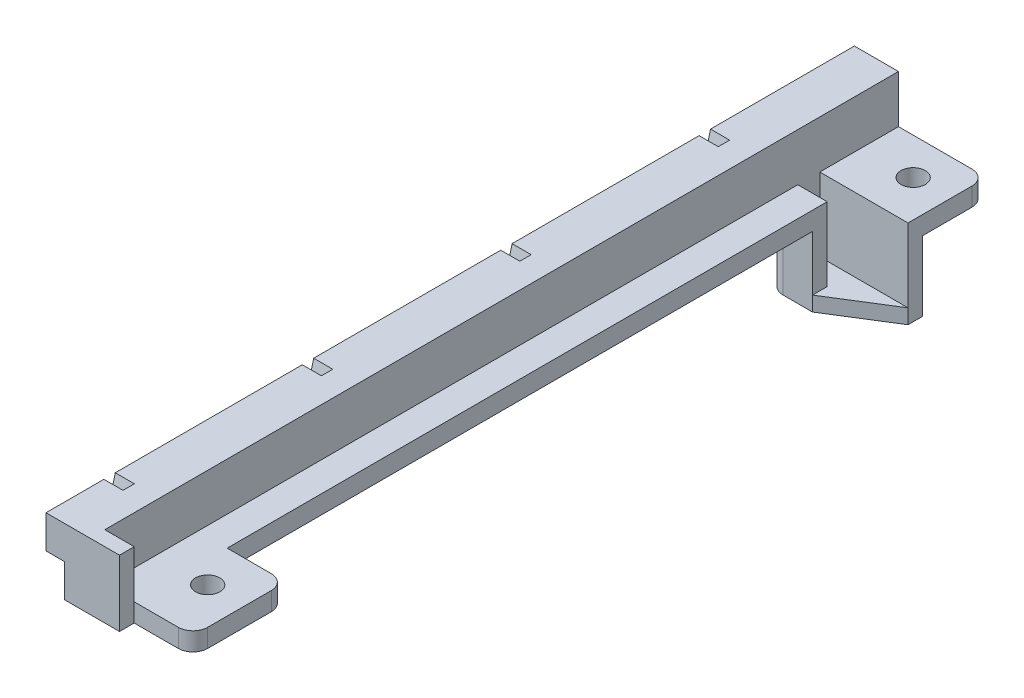
SolidWorks part; units mm, degrees
ref_plane "Front Plane" through (0, 0, 0) normal (0, 0, 1) x (1, 0, 0)
ref_plane "Top Plane" through (0, 0, 0) normal (0, 1, 0) x (1, 0, 0)
ref_plane "Right Plane" through (0, 0, 0) normal (1, 0, 0) x (0, 0, -1)
sketch "Side lip main section" plane through (0, 0, 0) normal (0, 1, 0) x (1, 0, 0)
  line L1 (0, 0) -> (6, 0)
  line L2 (0, 0) -> (0, -108)
  line L3 (0, -108) -> (6, -108)
  line L4 (6, 0) -> (6, -108)
  dimension "D1" = 6
  dimension "D2" = 108
extrude "Side lip" add sketch "Side lip main section" against normal blind 5
sketch "Sketch2" plane through (0, 0, 0) normal (-1, 0, 0) x (0, 0, 1)
  line L0 (102, 0) -> (103.2466, -5)
  line L1 (0, 0) -> (108, 0) construction
  line L2 (0, -5) -> (108, -5) construction
  line L3 (100.4541, 0) -> (101.7007, -5)
  line L4 (75, 0) -> (76.2466, -5)
  line L5 (73.4541, 0) -> (74.7007, -5)
  line L6 (48, 0) -> (49.2466, -5)
  line L7 (46.4541, 0) -> (47.7007, -5)
  line L8 (21, 0) -> (22.2466, -5)
  line L9 (19.4541, 0) -> (20.7007, -5)
  line L10 (21, 0) -> (19.5446, -0.3629) construction
  line L11 (48, 0) -> (46.5446, -0.3629) construction
  line L12 (75, 0) -> (73.5446, -0.3629) construction
  line L13 (102, 0) -> (100.5446, -0.3629) construction
  line L14 (102, 0) -> (102, -5) construction
  line L15 (108, -5) -> (108, 0) construction
  line L16 (75, 0) -> (75, -5) construction
  line L17 (48, 0) -> (48, -5) construction
  line L18 (21, 0) -> (21, -5) construction
  line L19 (19.4541, 0) -> (21, 0)
  line L20 (20.7007, -5) -> (22.2466, -5)
  line L21 (47.7007, -5) -> (49.2466, -5)
  line L22 (46.4541, 0) -> (48, 0)
  line L23 (73.4541, 0) -> (75, 0)
  line L24 (74.7007, -5) -> (76.2466, -5)
  line L25 (100.4541, 0) -> (102, 0)
  line L26 (101.7007, -5) -> (103.2466, -5)
  dimension "D1" = 1.5
  dimension "D2" = 76
  dimension "D3" = 6
  dimension "D4" = 27
  dimension "D5" = 54
  dimension "D6" = 81
extrude "Vertical fin cuts" cut sketch "Sketch2" against normal blind 2.6
sketch "Sketch4" plane through (0, -5, 0) normal (0, -1, 0) x (1, 0, 0)
  line L0 (6, 0) -> (0, 0) construction
  line L1 (6, 108) -> (2.5, 108)
  line L2 (6, 108) -> (6, 0)
  line L3 (6, 0) -> (2.5, 0)
  line L4 (2.5, 108) -> (2.5, 0)
  dimension "D1" = 3.5
extrude "Descender" add sketch "Sketch4" along normal blind 4.5
sketch "Sketch5" plane through (6, 0, 0) normal (1, 0, 0) x (0, 0, -1)
  line L0 (0, -9.5) -> (0, 0) construction
  line L1 (-108, -9.5) -> (0, -9.5)
  line L2 (-108, -9.5) -> (-108, -7)
  line L3 (-108, -7) -> (0, -7)
  line L4 (0, -9.5) -> (0, -7)
  dimension "D1" = 2.5
extrude "PCB base" add sketch "Sketch5" along normal blind 4
sketch "Sketch8" plane through (0, 0, 108) normal (0, 0, 1) x (1, 0, 0)
  line L1 (6, 0) -> (10, 0)
  line L4 (10, 0) -> (10, -7)
  line L8 (6, 0) -> (0, 0)
  line L9 (0, 0) -> (0, -5)
  line L10 (0, -5) -> (2.5, -5)
  line L11 (2.5, -5) -> (2.5, -9.5)
  line L12 (2.5, -9.5) -> (10, -9.5)
  line L13 (10, -9.5) -> (10, -7)
  line L14 (10, -7) -> (6, -7)
  line L15 (6, -7) -> (6, 0)
  line L16 (6, 0) -> (0, 0)
  line L17 (0, 0) -> (0, -5)
  line L18 (0, -5) -> (2.5, -5)
  line L19 (2.5, -5) -> (2.5, -9.5)
  line L20 (2.5, -9.5) -> (10, -9.5)
  line L21 (10, -9.5) -> (10, -7)
  dimension "D1" = 0
extrude "Lower cap" add sketch "Sketch8" along normal blind 2
sketch "Sketch9" plane through (10, 0, 0) normal (1, 0, 0) x (0, 0, -1)
  line L0 (0, -7) -> (-108, -7) construction
  line L1 (-13.7, -7) -> (-10.7, -7)
  line L2 (-13.7, -7) -> (-13.7, -9.5)
  line L3 (-13.7, -9.5) -> (-10.7, -9.5)
  line L4 (-10.7, -7) -> (-10.7, -9.5)
  line L5 (-110, -9.5) -> (0, -9.5) construction
  line L6 (-108, -7) -> (-108, 0) construction
  dimension "D1" = 94.3
  dimension "D2" = 3
extrude "Al bar cut" cut sketch "Sketch9" against normal blind 4
sketch "Sketch10" plane through (10, 0, 0) normal (1, 0, 0) x (0, 0, -1)
  line L0 (-110, -9.5) -> (-13.7, -9.5) construction
  line L1 (-108, -7) -> (-95.3463, -7)
  line L2 (-108, -7) -> (-108, -9.5)
  line L3 (-108, -9.5) -> (-95.3463, -9.5)
  line L4 (-95.3463, -7) -> (-95.3463, -9.5)
  line L6 (-10.7, -7) -> (0, -7)
  line L7 (-10.7, -7) -> (-10.7, -9.5)
  line L8 (-10.7, -9.5) -> (0, -9.5)
  line L9 (0, -7) -> (0, -9.5)
extrude "Support tabs" add sketch "Sketch10" along normal blind 8
sketch "Sketch11" plane through (0, -7, 0) normal (0, 1, 0) x (1, 0, 0)
  line L0 (13, 0) -> (13, -108) construction
  line L5 (18, 0) -> (6, 0) construction
  line L6 (18, -108) -> (10, -108) construction
  line L7 (6, 0) -> (6, -10.7) construction
  line L8 (6, -101) -> (18, -101) construction
  line L9 (6, -13.7) -> (6, -108) construction
  line L10 (18, -95.3463) -> (18, -108) construction
  line L11 (6, -5) -> (18, -5) construction
  line L12 (18, 0) -> (18, -10.7) construction
  circle A0 centre (13, -5) radius 1.65
  circle A1 centre (13, -101) radius 1.65
  dimension "D4" = 3.3
  dimension "D1" = 7
  dimension "D2" = 7
  dimension "D3" = 103
extrude "Bolt holes" cut sketch "Sketch11" against normal up to next
sketch "Sketch12" plane through (0, -9.5, 0) normal (0, -1, 0) x (1, 0, 0)
  line L0 (6, 10.7) -> (18, 10.7) construction
  line L1 (6, 13.7) -> (6, 10.7) construction
  line L2 (6, 13.7) -> (10, 13.7) construction
  line L3 (6, 10.7) -> (18, 10.7)
  line L4 (6, 13.7) -> (6, 10.7)
  line L5 (6, 13.7) -> (10, 13.7)
  line L6 (4, 15.7) -> (10, 15.7)
  line L7 (4, 15.7) -> (4, 8.7)
  line L8 (4, 8.7) -> (18, 8.7)
  line L9 (10, 15.7) -> (10, 13.7)
  line L10 (18, 10.7) -> (18, 8.7)
  dimension "D1" = 2
extrude "Al bar enclosure" add sketch "Sketch12" along normal blind 7.5
sketch "Sketch13" plane through (0, -17, 0) normal (0, -1, 0) x (1, 0, 0)
  line L1 (10, 15.7) -> (4, 15.7) construction
  line L2 (4, 15.7) -> (4, 8.7) construction
  line L3 (4, 8.7) -> (18, 8.7) construction
  line L4 (18, 8.7) -> (18, 10.7) construction
  line L6 (10, 15.7) -> (4, 15.7)
  line L7 (4, 15.7) -> (4, 8.7)
  line L8 (4, 8.7) -> (18, 8.7)
  line L9 (18, 8.7) -> (18, 10.7)
  line L10 (18, 10.7) -> (10, 15.7)
extrude "Al bar base" add sketch "Sketch13" along normal blind 2 contours L10 L6 L7 L8 L9
fillet "Fillet1" radius 2 5 edges at (4, -14.25, 8.7) (4, -14.25, 15.7) (18, -8.25, 95.3463) (18, -8.25, 108) (18, -8.25, 0)
sketch "Sketch16" plane through (0, 0, 110) normal (0, 0, 1) x (1, 0, 0)
  line L0 (10, -9.5) -> (10, 0) construction
  line L1 (0, 0) -> (10, 0)
  line L2 (0, 0) -> (0, -0.5)
  line L3 (0, -0.5) -> (10, -0.5)
  line L4 (10, 0) -> (10, -0.5)
  dimension "D1" = 0.5
extrude "Reduce side support height" cut sketch "Sketch16" against normal through all
